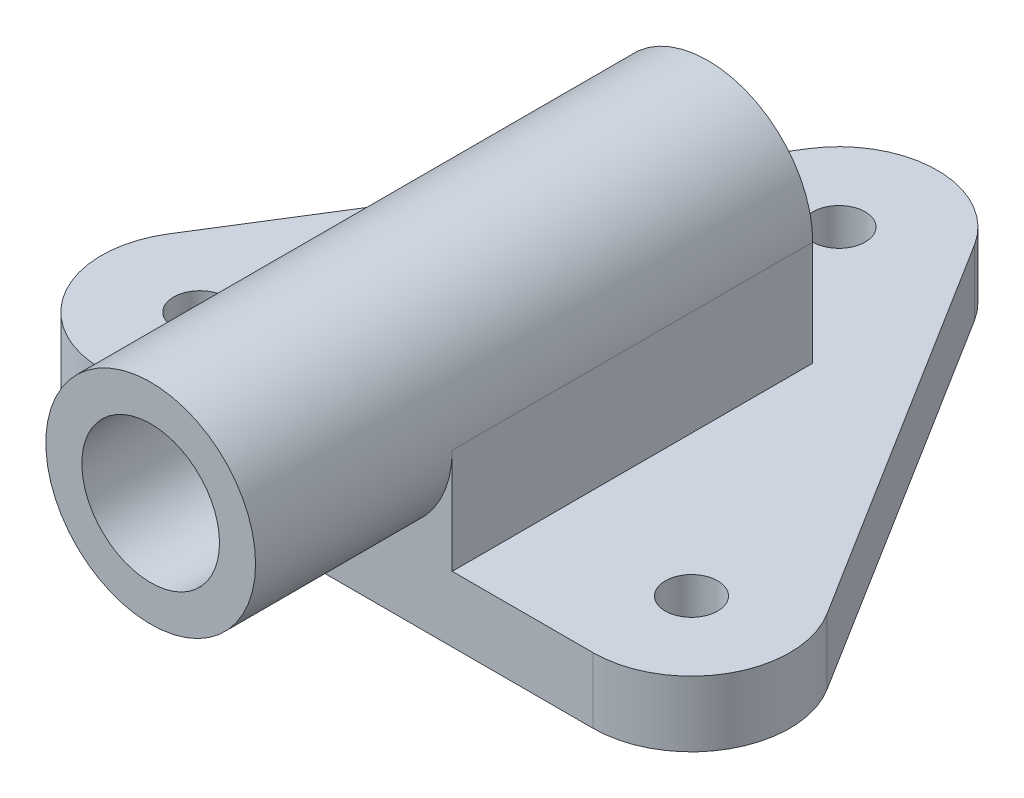
SolidWorks part; units mm, degrees
ref_plane "Front Plane" through (0, 0, 0) normal (0, 0, 1) x (1, 0, 0)
ref_plane "Top Plane" through (0, 0, 0) normal (0, 1, 0) x (1, 0, 0)
ref_plane "Right Plane" through (0, 0, 0) normal (1, 0, 0) x (0, 0, -1)
sketch "Sketch1" plane through (0, 0, 0) normal (0, 1, 0) x (1, 0, 0)
  line L0 (-12.72, 7.95) -> (-50.22, -52.05)
  line L1 (-37.5, -75) -> (37.5, -75)
  line L2 (50.22, -52.05) -> (12.72, 7.95)
  line L3 (0, 0) -> (0, 42.4624) construction
  circle A0 centre (0, 0) radius 4
  arc A1 (12.72, 7.95) -> (-12.72, 7.95) centre (0, 0) ccw
  circle A2 centre (-37.5, -60) radius 4
  circle A3 centre (37.5, -60) radius 4
  arc A4 (-37.5, -75) -> (-50.22, -52.05) centre (-37.5, -60) cw
  arc A5 (50.22, -52.05) -> (37.5, -75) centre (37.5, -60) cw
  point P10 (0, 28.3019)
  point P19 (0, 0)
  point P20 (0, 0)
  point P21 (0, 0)
  dimension "D1" = 8
  dimension "D2" = 15
  dimension "D3" = 15
  dimension "D4" = 15
  dimension "D7" = 8
  dimension "D8" = 8
  dimension "D5" = 75
  dimension "D6" = 60
extrude "Boss-Extrude1" add sketch "Sketch1" along normal blind 10 contours L3 L1 A5 L2 A1 A0 A3 | L1 L3 A0 A1 L0 A4 A2 region at (0, 0, 40.2884)
sketch "Sketch2" plane through (0, 0, 75) normal (0, 0, 1) x (1, 0, 0)
  line L0 (-37.5, 10) -> (37.5, 10) construction
  line L1 (-16, 26) -> (-16, 10)
  line L2 (16, 26) -> (16, 10)
  circle A0 centre (0, 26) radius 10.5
  circle A1 centre (0, 26) radius 16
  line M5 (37.5, 10) -> (-37.5, 10)
  dimension "D1" = 32
  dimension "D2" = 21
extrude "Boss-Extrude2" add sketch "Sketch2" along normal blind 30 separate body contours A1 A0 region at (0, 10.4525, 75)
extrude "Boss-Extrude3" add sketch "Sketch2<3>" against normal blind 55 contours A1 A0 region at (0, 10.4525, 75)
sketch "Sketch2<3>" plane through (0, 0, 75) normal (0, 0, 1) x (1, 0, 0) same geometry as "Sketch2"
extrude "Boss-Extrude4" add sketch "Sketch2<4>" against normal blind 55 contours A1 L2 M5 | A1 L1 M5 region at (-12.4261, 13.5739, 75) region at (12.4261, 13.5739, 75)
sketch "Sketch2<4>" plane through (0, 0, 75) normal (0, 0, 1) x (1, 0, 0) same geometry as "Sketch2"
